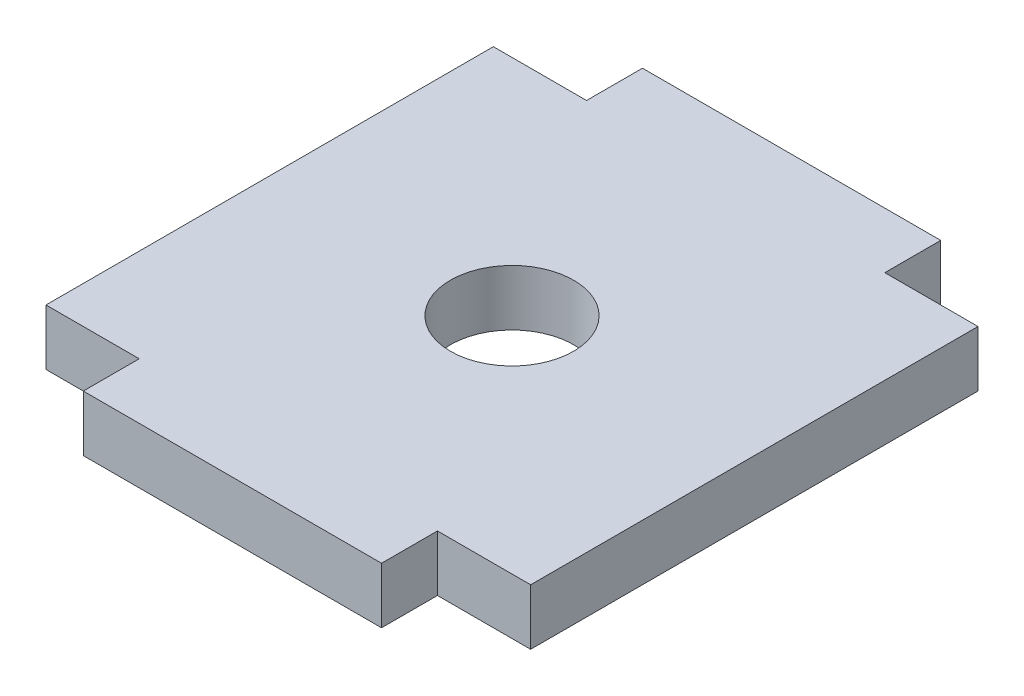
SolidWorks part; units mm, degrees
ref_plane "Alzado" through (0, 0, 0) normal (0, 0, 1) x (1, 0, 0)
ref_plane "Planta" through (0, 0, 0) normal (0, 1, 0) x (1, 0, 0)
ref_plane "Vista lateral" through (0, 0, 0) normal (1, 0, 0) x (0, 0, -1)
sketch "Croquis1" plane through (0, 0, 0) normal (0, 1, 0) x (1, 0, 0)
  line L0 (0, 0) -> (0, 24)
  line L1 (0, 24) -> (5, 24)
  line L2 (26, 24) -> (26, 0)
  line L3 (26, 0) -> (21, 0)
  line L4 (5, 0) -> (0, 0)
  line L5 (21, 27) -> (5, 27)
  line L6 (5, 27) -> (5, 24)
  line L7 (21, 27) -> (21, 24)
  line L9 (21, -3) -> (21, 0)
  line L10 (5, -3) -> (5, 0)
  line L11 (21, -3) -> (5, -3)
  line L13 (21, 24) -> (26, 24)
  circle A0 centre (13, 12) radius 3.3048
  dimension "D1" = 24
  dimension "D2" = 26
extrude "Saliente-Extruir1" add sketch "Croquis1" along normal blind 3
